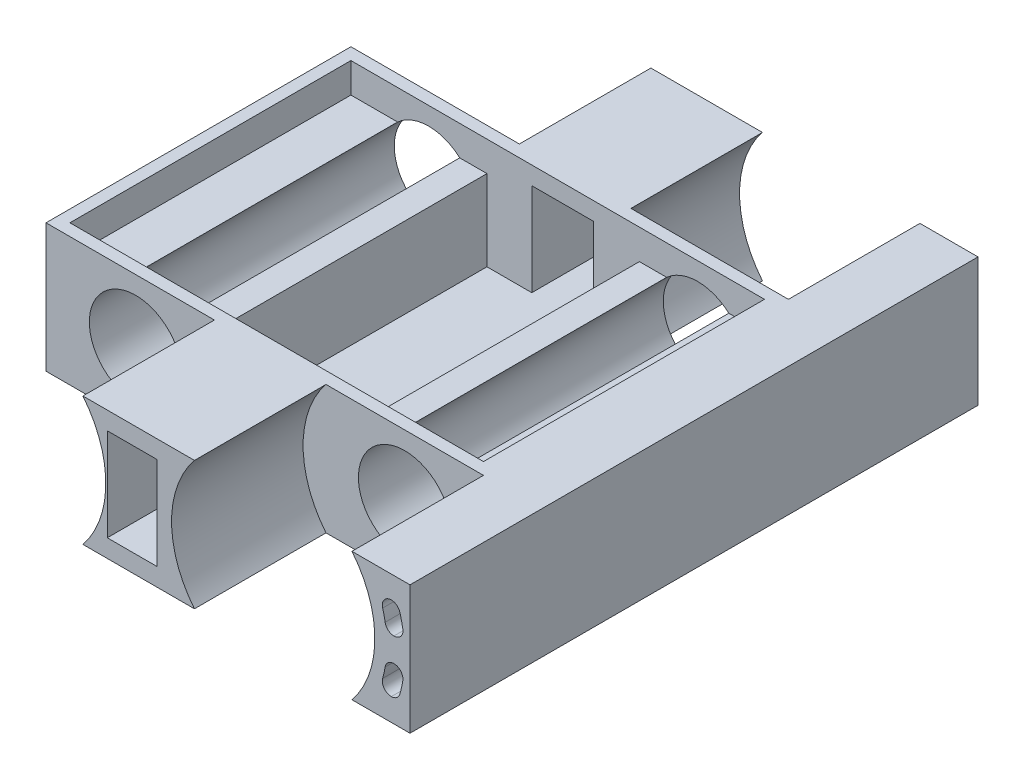
SolidWorks part; units mm, degrees
ref_plane "Front Plane" through (0, 0, 0) normal (0, 0, 1) x (1, 0, 0)
ref_plane "Top Plane" through (0, 0, 0) normal (0, 1, 0) x (1, 0, 0)
ref_plane "Right Plane" through (0, 0, 0) normal (1, 0, 0) x (0, 0, -1)
sketch "Sketch1" plane through (0, 0, 0) normal (0, 1, 0) x (1, 0, 0)
  line L1 (-44.2281, 29.9937) -> (50.7719, 29.9937)
  line L2 (-44.2281, 29.9937) -> (-44.2281, -65.0063)
  line L3 (-44.2281, -65.0063) -> (50.7719, -65.0063)
  line L4 (50.7719, 29.9937) -> (50.7719, -65.0063)
  dimension "D1" = 95
  dimension "D2" = 95
extrude "Boss-Extrude1" add sketch "Sketch1" along normal blind 25
sketch "Sketch2" plane through (0, 0, 65.0063) normal (0, 0, 1) x (1, 0, 0)
  line L1 (-44.2281, 0) -> (50.7719, 0) construction
  line L2 (-44.2281, 25) -> (-44.2281, 0) construction
  circle A0 centre (-29.2281, 10.75) radius 7.75
  circle A1 centre (15.7719, 10.75) radius 7.75
  point P6 (-44.2281, 12.5)
  dimension "D1" = 45
  dimension "D2" = 10.75
  dimension "D3" = 15
extrude "Cut-Extrude2" cut sketch "Sketch2" against normal blind 100
sketch "Sketch3" plane through (0, 0, 65.0063) normal (0, 0, 1) x (1, 0, 0)
  line L0 (-44.2281, 0) -> (50.7719, 0) construction
  circle A0 centre (-29.2281, 10.75) radius 17
  circle A1 centre (15.7719, 10.75) radius 17
  point P7 (-28.0903, 8.1892)
  dimension "D1" = 45
  dimension "D2" = 10.75
extrude "Cut-Extrude3" cut sketch "Sketch3" against normal blind 22
sketch "Sketch4" plane through (0, 0, -29.9937) normal (0, 0, -1) x (-1, 0, 0)
  circle A0 centre (-15.7719, 10.75) radius 17
  circle A1 centre (29.2281, 10.75) radius 17
extrude "Cut-Extrude4" cut sketch "Sketch4" against normal blind 22
sketch "Sketch5" plane through (0, 0, 65.0063) normal (0, 0, 1) x (1, 0, 0)
  line L1 (-44.2281, 25) -> (-37.9811, 25)
  line L2 (-44.2281, 25) -> (-44.2281, 0)
  line L3 (-44.2281, 0) -> (-37.9811, 0)
  line L4 (-37.9811, 25) -> (-37.9811, 0)
extrude "Cut-Extrude5" cut sketch "Sketch5" against normal blind 22
sketch "Sketch6" plane through (0, 0, -29.9937) normal (0, 0, -1) x (-1, 0, 0)
  line L1 (44.2281, 25) -> (37.0493, 25)
  line L2 (44.2281, 25) -> (44.2281, 0)
  line L3 (44.2281, 0) -> (37.0493, 0)
  line L4 (37.0493, 25) -> (37.0493, 0)
extrude "Cut-Extrude6" cut sketch "Sketch6" against normal blind 22
sketch "Sketch8" plane through (0, 0, -29.9937) normal (0, 0, -1) x (-1, 0, 0)
  line L1 (-50.7719, 25) -> (48.732, 25)
  line L2 (-50.7719, 25) -> (-50.7719, 21.5)
  line L3 (-50.7719, 21.5) -> (48.732, 21.5)
  line L4 (48.732, 25) -> (48.732, 21.5)
  dimension "D1" = 3.5
extrude "Cut-Extrude7" cut sketch "Sketch8" against normal blind 100
sketch "Sketch9" plane through (0, 0, 65.0063) normal (0, 0, 1) x (1, 0, 0)
  line L0 (-16.0585, 0) -> (2.6024, 0) construction
  line L1 (-11.9781, 18.5) -> (-3.6781, 18.5)
  line L2 (-11.9781, 18.5) -> (-11.9781, 3)
  line L3 (-11.9781, 3) -> (-3.6781, 3)
  line L4 (-3.6781, 18.5) -> (-3.6781, 3)
  arc A0 (-16.0585, 0) -> (-16.0585, 21.5) centre (-29.2281, 10.75) ccw construction
  circle A1 centre (15.7719, 10.75) radius 7.75 construction
  dimension "D1" = 8.3
  dimension "D2" = 15.5
  dimension "D3" = 3
  dimension "D4" = 17.25
  dimension "D5" = 19.45
extrude "Cut-Extrude11" cut sketch "Sketch9" against normal blind 100
sketch "Sketch13" plane through (-3.6781, 0, 0) normal (-1, 0, 0) x (0, 0, 1)
  line L0 (-29.9937, 3) -> (65.0063, 3) construction
  line L1 (-25.9937, 3) -> (61.0063, 3)
  line L2 (-25.9937, 3) -> (-25.9937, 18.5)
  line L3 (-25.9937, 18.5) -> (61.0063, 18.5)
  line L4 (61.0063, 3) -> (61.0063, 18.5)
  line L5 (-29.9937, 18.5) -> (65.0063, 18.5) construction
  line L6 (-29.9937, 3) -> (-29.9937, 18.5) construction
  line L7 (65.0063, 3) -> (65.0063, 18.5) construction
  dimension "D1" = 4
  dimension "D2" = 4
extrude "Cut-Extrude12" cut sketch "Sketch13" against normal blind 2
sketch "Sketch14" plane through (0, 21.5, 0) normal (0, 1, 0) x (1, 0, 0)
  line L2 (6.0219, 5.9937) -> (6.0219, -41.0063)
  line L4 (-19.4781, 5.9937) -> (-19.4781, -41.0063)
  line L7 (6.0219, 5.9937) -> (-19.4781, 5.9937)
  line L9 (6.0219, -41.0063) -> (-19.4781, -41.0063)
  dimension "D2" = 2
extrude "Cut-Extrude14" cut sketch "Sketch14" against normal blind 18.5
sketch "Sketch16" plane through (0, 21.5, 0) normal (0, 1, 0) x (1, 0, 0)
  line L0 (-44.2281, -43.0063) -> (-44.2281, 7.9937) construction
  line L1 (-17.4781, 5.9937) -> (-42.2281, 5.9937)
  line L2 (-17.4781, 5.9937) -> (-17.4781, -41.0063)
  line L3 (-17.4781, -41.0063) -> (-42.2281, -41.0063)
  line L4 (-42.2281, 5.9937) -> (-42.2281, -41.0063)
  line L5 (-44.2281, -43.0063) -> (-16.0585, -43.0063) construction
  line L6 (-16.0585, 7.9937) -> (-44.2281, 7.9937) construction
  dimension "D1" = 2
  dimension "D2" = 2
  dimension "D3" = 2
  dimension "D4" = 2
extrude "Cut-Extrude15" cut sketch "Sketch16" against normal blind 5
sketch "Sketch17" plane through (0, 21.5, 0) normal (0, 1, 0) x (1, 0, 0)
  line L0 (2.6024, -43.0063) -> (28.9415, -43.0063) construction
  line L1 (6.0219, 5.9937) -> (26.9415, 5.9937)
  line L2 (6.0219, 5.9937) -> (6.0219, -41.0063)
  line L3 (6.0219, -41.0063) -> (26.9415, -41.0063)
  line L4 (26.9415, 5.9937) -> (26.9415, -41.0063)
  dimension "D1" = 2
  dimension "D2" = 2
extrude "Cut-Extrude16" cut sketch "Sketch17" against normal blind 5
sketch "Sketch18" plane through (0, 0, 65.0063) normal (0, 0, 1) x (1, 0, 0)
  line L0 (34.6664, 12.75) -> (37.6809, 12.75)
  line L2 (34.6664, 8.75) -> (37.6809, 8.75)
  line L3 (33.4355, 17.75) -> (36.6286, 17.75)
  line L4 (33.4355, 3.75) -> (36.6286, 3.75)
  arc A0 (36.6286, 3.75) -> (37.6809, 8.75) centre (15.7719, 10.75) ccw
  arc A1 (33.4355, 3.75) -> (34.6664, 8.75) centre (15.7719, 10.75) ccw
  arc A2 (34.6664, 12.75) -> (33.4355, 17.75) centre (15.7719, 10.75) ccw
  arc A3 (37.6809, 12.75) -> (36.6286, 17.75) centre (15.7719, 10.75) ccw
  dimension "D1" = 44
  dimension "D2" = 38
  dimension "D4" = 5
  dimension "D6" = 5
extrude "Cut-Extrude17" cut sketch "Sketch18" against normal blind 100
fillet "Fillet6" radius 1.5 2 edges at (33.4355, 17.75, 17.5063) (36.6286, 17.75, 17.5063)
fillet "Fillet7" radius 1.5 2 edges at (37.6809, 12.75, 17.5063) (34.6664, 12.75, 17.5063)
fillet "Fillet8" radius 1.5 2 edges at (33.4355, 3.75, 17.5063) (36.6286, 3.75, 17.5063)
fillet "Fillet9" radius 1.5 2 edges at (37.6809, 8.75, 17.5063) (34.6664, 8.75, 17.5063)
sketch "Sketch19" plane through (0, 0, 65.0063) normal (0, 0, 1) x (1, 0, 0)
  line L1 (28.9415, 0) -> (50.7719, 0) construction
  line L2 (38.6507, 0) -> (50.7719, 0)
  line L3 (38.6507, 0) -> (38.6507, 21.5)
  line L4 (38.6507, 21.5) -> (50.7719, 21.5)
  line L5 (50.7719, 0) -> (50.7719, 21.5)
extrude "Cut-Extrude20" cut sketch "Sketch19" against normal blind 100
